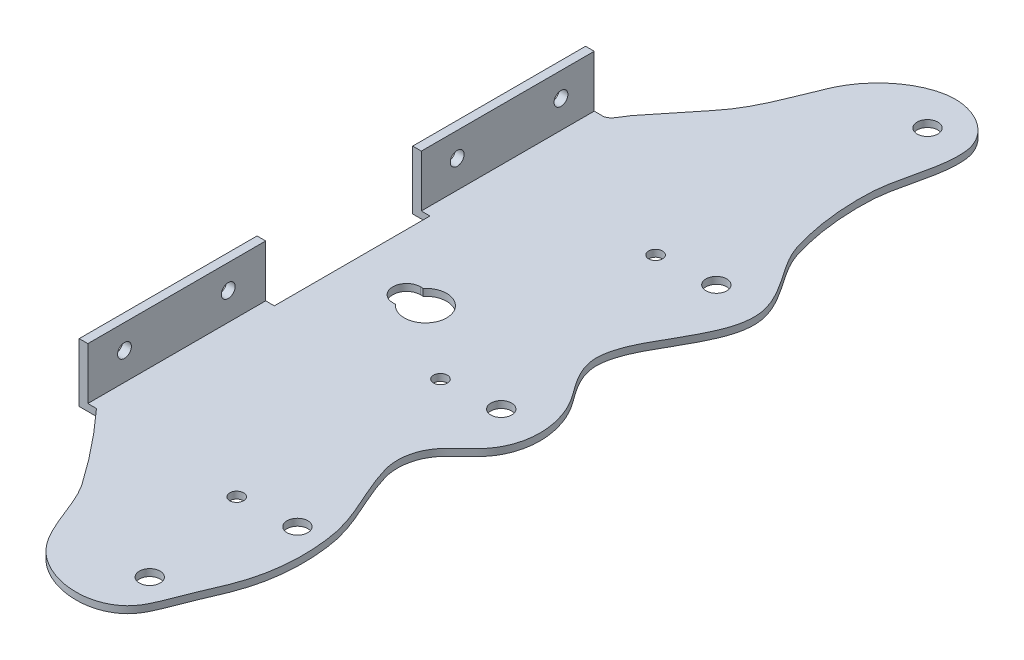
SolidWorks part; units mm, degrees
material "6061-T6 (SS)"
ref_plane "Alzado" through (0, 0, 0) normal (0, 0, 1) x (1, 0, 0)
ref_plane "Planta" through (0, 0, 0) normal (0, 1, 0) x (1, 0, 0)
ref_plane "Vista lateral" through (0, 0, 0) normal (1, 0, 0) x (0, 0, -1)
ref_plane "Plano1" through (0, 0, 0) normal (0, -1, 0) x (1, 0, 0)
sketch "Croquis1" plane through (0, 0, 0) normal (0, -1, 0) x (1, 0, 0)
  line L0 (404.2985, -1165.2643) -> (404.2985, -1311.6829)
  arc A0 (404.2985, -1165.2643) -> (421.4368, -1143.838) centre (255.6611, -1028.8056) ccw
  spline S0 degree 3 poles (404.2985, -1311.6829) (406.2956, -1311.7367) (407.085, -1314.4488) (409.5752, -1317.5435) (410.8203, -1319.0908) (414.5556, -1323.7328) (417.0649, -1326.8) (424.5132, -1336.3101) (426.8532, -1344.0451) (433.1714, -1358.7078) (440.2464, -1365.1551) (456.0885, -1368.0934) (464.9999, -1362.9326) (466.1658, -1346.9151) (462.4736, -1339.1903) (461.7627, -1323.2582) (462.7216, -1315.292) (467.1604, -1300.0675) (474.1763, -1294.5055) (477.9549, -1278.7237) (472.7345, -1270.9766) (465.1057, -1257.2725) (463.3269, -1252.4306) (464.7213, -1244.2656) (467.3242, -1240.8052) (474.8596, -1230.459) (476.349, -1220.8082) (469.7158, -1209.8114) (465.878, -1207.5713) (460.805, -1200.6115) (460.1335, -1195.934) (463.62, -1183.5494) (468.6543, -1176.2132) (471.5048, -1159.3523) (471.1045, -1150.5179) (466.8847, -1138.4173) (465.012, -1134.5734) (461.8421, -1126.6151) (460.6334, -1122.1798) (450.4899, -1114.2459) (439.6601, -1115.9446) (427.1441, -1127.1801) (426.028, -1136.6775) (421.4368, -1143.838) knots 0 0 0 0 0.015625 0.015625 0.03125 0.03125 0.0625 0.0625 0.125 0.125 0.1875 0.1875 0.25 0.25 0.3125 0.3125 0.375 0.375 0.4375 0.4375 0.5 0.5 0.53125 0.53125 0.5625 0.5625 0.625 0.625 0.65625 0.65625 0.6875 0.6875 0.75 0.75 0.8125 0.8125 0.84375 0.84375 0.875 0.875 0.9375 0.9375 1 1 1 1
extrude "Saliente-Extruir1" add sketch "Croquis1" against normal blind 2
sketch "Croquis2" plane through (404.2985, 0, 0) normal (-1, 0, 0) x (0, 0, 1)
  line L0 (-1311.6829, 2) -> (-1261.6829, 2)
  line L1 (-1261.6829, 2) -> (-1261.6829, 0)
  line L2 (-1261.6829, 0) -> (-1311.6829, 0)
  line L3 (-1311.6829, 0) -> (-1311.6829, 2)
extrude "Saliente-Extruir2" add sketch "Croquis2" along normal blind 5.0048
sketch "Croquis3" plane through (0, 2, 0) normal (0, 1, 0) x (-1, 0, 0)
  line L0 (-399.2937, -1261.6829) -> (-399.2937, -1311.6829)
  line L1 (-399.2937, -1311.6829) -> (-401.7961, -1311.6829)
  line L2 (-401.7961, -1311.6829) -> (-401.7961, -1261.6829)
  line L3 (-401.7961, -1261.6829) -> (-399.2937, -1261.6829)
extrude "Saliente-Extruir3" add sketch "Croquis3" along normal blind 15
sketch "Croquis4" plane through (404.2985, 0, 0) normal (-1, 0, 0) x (0, 0, 1)
  line L0 (-1216.6829, 2) -> (-1165.2643, 2)
  line L1 (-1165.2643, 2) -> (-1165.2643, 0)
  line L2 (-1165.2643, 0) -> (-1216.6829, 0)
  line L3 (-1216.6829, 0) -> (-1216.6829, 2)
extrude "Saliente-Extruir4" add sketch "Croquis4" along normal blind 5.0048
sketch "Croquis5" plane through (0, 2, 0) normal (0, 1, 0) x (-1, 0, 0)
  line L0 (-401.7961, -1165.2643) -> (-399.2937, -1165.2643)
  line L1 (-399.2937, -1165.2643) -> (-399.2937, -1216.6829)
  line L2 (-399.2937, -1216.6829) -> (-401.7961, -1216.6829)
  line L3 (-401.7961, -1216.6829) -> (-401.7961, -1165.2643)
extrude "Saliente-Extruir5" add sketch "Croquis5" along normal blind 15
sketch "Croquis6" plane through (0, 0, 0) normal (0, -1, 0) x (1, 0, 0)
  line L0 (426.2664, -1295.2212) -> (430.29, -1290.2547)
  line L1 (430.29, -1290.2547) -> (426.1062, -1275.6941)
  line L2 (426.1062, -1275.6941) -> (430.239, -1263.7367)
  line L3 (430.239, -1263.7367) -> (420.8071, -1267.1618)
  line L4 (420.8071, -1267.1618) -> (415.4015, -1278.732)
  line L5 (415.4015, -1278.732) -> (415.4015, -1299.9626)
  line L6 (415.4015, -1299.9626) -> (435.8281, -1316.511)
  line L7 (435.8281, -1316.511) -> (426.2664, -1295.2212)
extrude "Cortar-Extruir1" cut sketch "Croquis6" against normal through all
sketch "Croquis7" plane through (0, 0, 0) normal (0, -1, 0) x (1, 0, 0)
  line L0 (435.4785, -1159.0929) -> (415.4015, -1176.1451)
  line L1 (415.4015, -1176.1451) -> (415.4015, -1194.6262)
  line L2 (415.4015, -1194.6262) -> (420.3188, -1205.5749)
  line L3 (420.3188, -1205.5749) -> (428.973, -1207.5821)
  line L4 (428.973, -1207.5821) -> (426.1062, -1197.9604)
  line L5 (426.1062, -1197.9604) -> (429.3639, -1183.9148)
  line L6 (429.3639, -1183.9148) -> (424.6459, -1178.7172)
  line L7 (424.6459, -1178.7172) -> (435.4785, -1159.0929)
extrude "Cortar-Extruir2" cut sketch "Croquis7" against normal through all
sketch "Croquis8" plane through (0, 2, 0) normal (0, 1, 0) x (-1, 0, 0)
  line L0 (-420.6488, -1234.5863) -> (-421.4368, -1234.5863)
  line L1 (-421.4368, -1242.5863) -> (-420.6488, -1242.5863)
  arc A0 (-420.6488, -1242.5863) -> (-420.6488, -1234.5863) centre (-420.6488, -1238.5863) ccw
  arc A1 (-421.4368, -1234.5863) -> (-421.4368, -1242.5863) centre (-426.0897, -1238.5863) cw
extrude "Cortar-Extruir3" cut sketch "Croquis8" against normal through all
ref_plane "Plano2" through (0, 0, -1238.5863) normal (0, 0, 1) x (1, 0, 0)
sketch "Croquis9" plane through (0, 0, -1238.5863) normal (0, 0, 1) x (1, 0, 0)
  line L0 (432.2256, 2) -> (426.0897, 2)
  line L1 (426.0897, 2) -> (426.0897, 0)
  line L2 (426.0897, 0) -> (432.2256, 0)
  line L3 (432.2256, 0) -> (432.2256, 2)
  line L4 (426.0897, 2) -> (426.0897, 0) construction
revolve "Cortar-Revolución1" cut sketch "Croquis9" angle 360 about L4 reverse direction yes
hole_wizard "Diámetro de taladro Ø4.0 (4)1" positions "Croquis11" profile "Croquis10" hole size "Ø4.0" standard "Ansi Metric"
sketch "Croquis11" plane through (0, 2, 0) normal (0, 1, 0) x (1, 0, 0)
  point P0 (446.6597, 1222.362)
  point P1 (446.6597, 1284.5572)
  point P2 (446.6597, 1163.427)
sketch "Croquis10" plane through (446.6597, 2, -1222.362) normal (1, 0, 0) x (0, 0, 1)
  line L0 (0, 0) -> (0, 1)
  line L1 (0, 1) -> (2, 1)
  line L2 (2, 1) -> (2, 0)
  line L5 (2, 0) -> (0, 0)
  line L10 (0, 1) -> (-2, 1) construction
  line L11 (0, -6.35) -> (0, 107.95) construction
  dimension "Diámetro de taladro" = 4
  dimension "Profundidad de taladro" = 1
  dimension "Ángulo de perforador" = 180
hole_wizard "Diámetro de taladro Ø4.0 (4)2" positions "Croquis13" profile "Croquis12" hole size "Ø4.0" standard "Ansi Metric"
sketch "Croquis13" plane through (0, 0, 0) normal (0, -1, 0) x (-1, 0, 0)
  point P0 (-462.9399, 1223.6491)
  point P1 (-454.1975, 1130.7574)
  point P2 (-462.9399, 1285.8444)
  point P3 (-462.9399, 1164.7141)
  point P4 (-454.1975, 1355.6291)
sketch "Croquis12" plane through (462.9399, 0, -1223.6491) normal (1, 0, 0) x (0, 0, -1)
  line L0 (0, 0) -> (0, 17)
  line L1 (0, 17) -> (2, 17)
  line L2 (2, 17) -> (2, 0)
  line L5 (2, 0) -> (0, 0)
  line L11 (0, -6.35) -> (0, 107.95) construction
  dimension "Diámetro de taladro hasta el siguiente" = 4
  dimension "Profundidad de taladro hasta el siguiente" = 17
hole_wizard "Diámetro de taladro Ø4.0 (4)3" positions "Croquis15" profile "Croquis14" hole size "Ø4.0" standard "Ansi Metric"
sketch "Croquis15" plane through (401.7961, 0, 0) normal (1, 0, 0) x (0, 0, -1)
  point P0 (1272.0558, 10)
  point P1 (1302.0558, 10)
  point P2 (1175.8558, 10)
  point P3 (1205.8558, 10)
sketch "Croquis14" plane through (401.7961, 10, -1272.0558) normal (0, 1, 0) x (0, 0, -1)
  line L0 (0, 0) -> (0, 2.5024)
  line L1 (0, 2.5024) -> (2, 2.5024)
  line L2 (2, 2.5024) -> (2, 0)
  line L5 (2, 0) -> (0, 0)
  line L11 (0, -6.35) -> (0, 107.95) construction
  dimension "Diámetro de taladro hasta el siguiente" = 4
  dimension "Profundidad de taladro hasta el siguiente" = 2.5024
hole_wizard "Taladro de margen para M31" positions "Croquis17" profile "Croquis16" hole size "M3" standard "Ansi Metric"
sketch "Croquis17" plane through (0, 2, 0) normal (0, 1, 0) x (1, 0, 0)
  point P0 (419.2222, 1220.9802)
  point P1 (420.3188, 1227.8197)
  point P2 (419.2222, 1256.1924)
  point P3 (420.3188, 1249.3529)
  point P4 (426.7161, 1252.5284)
  point P5 (426.7161, 1224.6442)
sketch "Croquis16" plane through (419.2222, 2, -1220.9802) normal (1, 0, 0) x (0, 0, 1)
  line L0 (0, 0) -> (0, 2)
  line L1 (0, 2) -> (1.72, 2)
  line L2 (1.72, 2) -> (1.72, 0)
  line L5 (1.72, 0) -> (0, 0)
  line L11 (0, -6.35) -> (0, 107.95) construction
  dimension "Diámetro de taladro hasta el siguiente" = 3.44
  dimension "Profundidad de taladro hasta el siguiente" = 2
sketch "Croquis18" plane through (0, 2, 0) normal (0, 1, 0) x (-1, 0, 0)
  line L0 (-435.4785, -1159.0929) -> (-415.4015, -1176.1451)
  line L1 (-424.6459, -1178.7172) -> (-435.4785, -1159.0929)
  line L2 (-429.3639, -1183.9148) -> (-424.6459, -1178.7172)
  line L3 (-415.4015, -1176.1451) -> (-415.4015, -1194.6262)
  line L4 (-415.4015, -1194.6262) -> (-420.3188, -1205.5749)
  line L5 (-420.3188, -1205.5749) -> (-428.973, -1207.5821)
  line L6 (-428.973, -1207.5821) -> (-426.1062, -1197.9604)
  line L7 (-426.1062, -1197.9604) -> (-429.3639, -1183.9148)
  line L8 (-415.4015, -1299.9626) -> (-415.4015, -1278.732)
  line L9 (-415.4015, -1278.732) -> (-420.8071, -1267.1618)
  line L10 (-420.8071, -1267.1618) -> (-430.239, -1263.7367)
  line L11 (-430.239, -1263.7367) -> (-426.1062, -1275.6941)
  line L12 (-426.1062, -1275.6941) -> (-430.29, -1290.2547)
  line L13 (-430.29, -1290.2547) -> (-426.2664, -1295.2212)
  line L14 (-426.2664, -1295.2212) -> (-435.8281, -1316.511)
  line L15 (-435.8281, -1316.511) -> (-415.4015, -1299.9626)
  arc A0 (-419.2222, -1222.7002) -> (-419.2222, -1219.2602) centre (-419.2222, -1220.9802) ccw
  arc A1 (-419.2222, -1219.2602) -> (-419.2222, -1222.7002) centre (-419.2222, -1220.9802) ccw
  arc A2 (-426.7161, -1222.9242) -> (-426.7161, -1226.3642) centre (-426.7161, -1224.6442) ccw
  arc A3 (-426.7161, -1226.3642) -> (-426.7161, -1222.9242) centre (-426.7161, -1224.6442) ccw
  arc A4 (-420.3188, -1229.5397) -> (-420.3188, -1226.0997) centre (-420.3188, -1227.8197) ccw
  arc A5 (-420.3188, -1226.0997) -> (-420.3188, -1229.5397) centre (-420.3188, -1227.8197) ccw
  arc A6 (-420.3188, -1247.6329) -> (-420.3188, -1251.0729) centre (-420.3188, -1249.3529) ccw
  arc A7 (-420.3188, -1251.0729) -> (-420.3188, -1247.6329) centre (-420.3188, -1249.3529) ccw
  arc A8 (-419.2222, -1257.9124) -> (-419.2222, -1254.4724) centre (-419.2222, -1256.1924) ccw
  arc A9 (-419.2222, -1254.4724) -> (-419.2222, -1257.9124) centre (-419.2222, -1256.1924) ccw
  arc A10 (-426.7161, -1250.8084) -> (-426.7161, -1254.2484) centre (-426.7161, -1252.5284) ccw
  arc A11 (-426.7161, -1254.2484) -> (-426.7161, -1250.8084) centre (-426.7161, -1252.5284) ccw
extrude "Saliente-Extruir6" add sketch "Croquis18" against normal up to surface (2 mm away) up to face at (419.2222, 0, -1219.2602)
ref_plane "Plano3" through (0, 2, 0) normal (0, 1, 0) x (1, 0, 0)
sketch "Croquis24" plane through (0, 2, 0) normal (0, 1, 0) x (1, 0, 0)
  circle A0 centre (446.6597, 1284.5572) radius 2
  circle A1 centre (446.6597, 1222.362) radius 2
  circle A2 centre (446.6597, 1163.427) radius 2
  circle A3 centre (454.1975, 1130.7574) radius 3
  circle A4 centre (462.9399, 1164.7141) radius 3
  circle A5 centre (462.9399, 1223.6491) radius 3
  circle A6 centre (462.9399, 1285.8444) radius 3
  circle A7 centre (454.1975, 1355.6291) radius 3
extrude "Cortar-Extruir4" cut sketch "Croquis24" against normal blind 10
